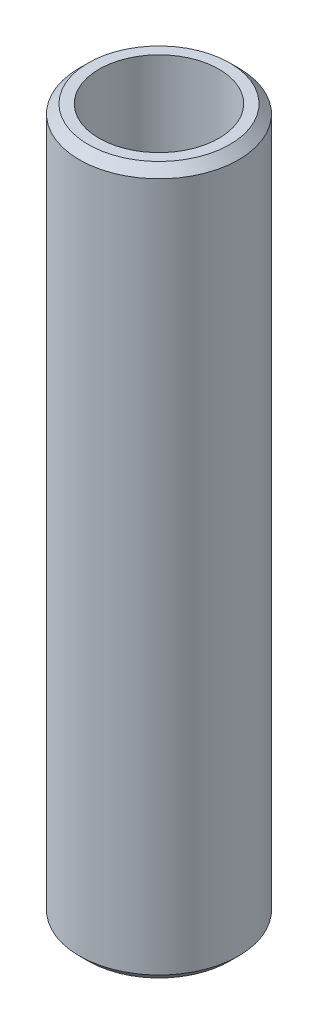
SolidWorks part; units mm, degrees
ref_plane "Front Plane" through (0, 0, 0) normal (0, 0, 1) x (1, 0, 0)
ref_plane "Top Plane" through (0, 0, 0) normal (0, 1, 0) x (1, 0, 0)
ref_plane "Right Plane" through (0, 0, 0) normal (1, 0, 0) x (0, 0, -1)
sketch "Sketch1" plane through (0, 0, 0) normal (0, 1, 0) x (1, 0, 0)
  circle A0 centre (0, 0) radius 52.5
  dimension "SHAFT_OD" = 105
extrude "Boss-Extrude1" add sketch "Sketch1" along normal blind 466.5861
sketch "Sketch2" plane through (0, 0, 0) normal (0, 1, 0) x (1, 0, 0)
  circle A0 centre (0, 0) radius 39.5441
  dimension "BORE_D" = 79.0882
extrude "Cut-Extrude1" cut sketch "Sketch2" along normal through all
chamfer "Chamfer1" distance 5.8087 angle 45 2 edges at (0, 466.5861, 52.5) (0, 0, 52.5)
